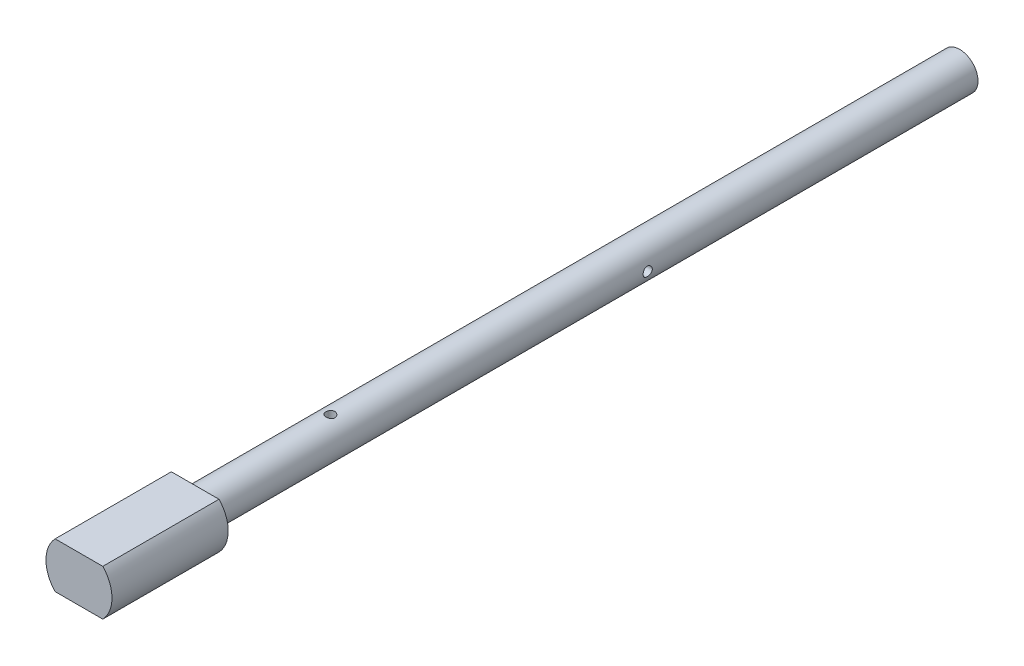
SolidWorks part; units mm, degrees
ref_plane "前视基准面" through (0, 0, 0) normal (0, 0, 1) x (1, 0, 0)
ref_plane "上视基准面" through (0, 0, 0) normal (0, 1, 0) x (1, 0, 0)
ref_plane "右视基准面" through (0, 0, 0) normal (1, 0, 0) x (0, 0, -1)
sketch "草图1" plane through (0, 0, 0) normal (0, 0, 1) x (1, 0, 0)
  circle A0 centre (0, 0) radius 1.5
  dimension "D1" = 3
extrude "凸台-拉伸1" add sketch "草图1" along normal blind 72
sketch "草图4" plane through (0, 0, 0) normal (0, 1, 0) x (1, 0, 0)
  circle A0 centre (0.1021, -51.55) radius 0.375
  dimension "D1" = 0.75
extrude "切除-拉伸3" cut sketch "草图4" against normal mid plane 4
sketch "草图5" plane through (0, 0, 72) normal (0, 0, 1) x (1, 0, 0)
  line L0 (0, 0) -> (-2.3094, 0) construction
  line L1 (1.9476, -1.87) -> (-1.9476, -1.87)
  line L3 (1.9476, 1.87) -> (-1.9476, 1.87)
  arc A0 (-1.9476, 1.87) -> (-1.9476, -1.87) centre (0, 0) ccw
  arc A2 (1.9476, -1.87) -> (1.9476, 1.87) centre (0, 0) ccw
  dimension "D1" = 5.4
  dimension "D2" = 3.74
extrude "凸台-拉伸2" add sketch "草图5" against normal offset from surface (9.5 mm away) 0.5
sketch "草图6" plane through (0, 0, 0) normal (1, 0, 0) x (0, 0, -1)
  circle A0 centre (-27, 0) radius 0.375
  dimension "D1" = 0.75
extrude "切除-拉伸4" cut sketch "草图6" against normal mid plane 3
